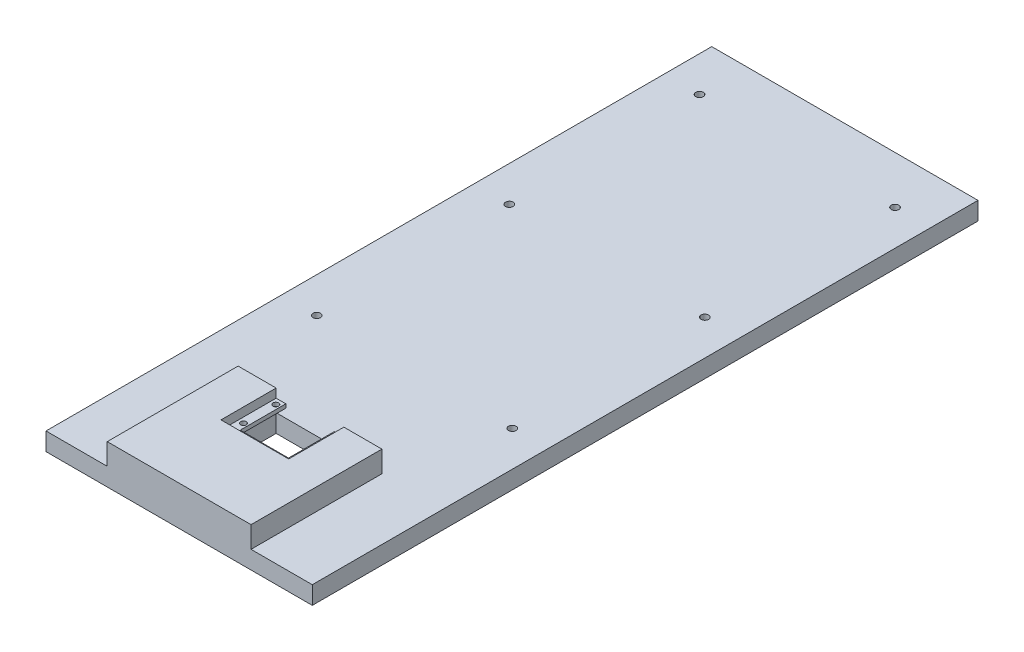
SolidWorks part; units mm, degrees
note: The reader was unsure of these and kept them because the rebuilt part matched: shared geometry of "Sketch5<5>".
ref_plane "Front Plane" through (0, 0, 0) normal (0, 0, 1) x (1, 0, 0)
ref_plane "Top Plane" through (0, 0, 0) normal (0, 1, 0) x (1, 0, 0)
ref_plane "Right Plane" through (0, 0, 0) normal (1, 0, 0) x (0, 0, -1)
sketch "Sketch2" plane through (0, 0, 0) normal (0, 1, 0) x (1, 0, 0)
  line L0 (-15, 0) -> (15, 0) construction
  line L1 (-15, 17) -> (15, 17) construction
  line L2 (-15, 17) -> (-15, -17) construction
  line L3 (-15, -17) -> (15, -17) construction
  line L4 (15, 17) -> (15, -17) construction
  line L5 (-8.5, -23.3) -> (8.5, -23.3) construction
  line L6 (0, 1064.2) -> (0, 64.2) construction
  line L8 (-17.8, -26.1) -> (17.8, -26.1) construction
  line L9 (-17.8, -26.1) -> (-17.8, 24.5) construction
  line L11 (17.8, -26.1) -> (17.8, 24.5) construction
  line L12 (-12.2, 24.5) -> (12.2, 24.5) construction
  line L13 (-12.2, 24.5) -> (-12.2, -20.5) construction
  line L14 (-12.2, -20.5) -> (12.2, -20.5) construction
  line L15 (12.2, 24.5) -> (12.2, -20.5) construction
  line L20 (-12.2, 24.5) -> (-17.8, 24.5) construction
  line L21 (12.2, 24.5) -> (17.8, 24.5) construction
  line L22 (-12.7, 25) -> (-12.7, -21)
  line L23 (-12.7, -21) -> (12.7, -21)
  line L24 (12.7, 25) -> (12.7, -21)
  line L25 (-12.7, 25) -> (12.7, 25)
  line L26 (37.8, -46.1) -> (37.8, 44.5)
  line L30 (-37.8, -46.1) -> (-37.8, 44.5)
  line L32 (37.8, -0.8) -> (37.8, -65.8)
  line L33 (37.8, -65.8) -> (37.8, 64.2)
  line L34 (37.8, 64.2) -> (-37.8, 64.2)
  line L35 (-37.8, 64.2) -> (-37.8, -65.8)
  line L36 (-37.8, -65.8) -> (37.8, -65.8)
  line L39 (-22.8, -62.2) -> (-37.8, -62.2) construction
  line L41 (9.15, 64.2) -> (9.15, 63.8) construction
  line L42 (9.15, -65.8) -> (-9.05, -65.8) construction
  line L44 (37.8, -65.8) -> (37.8, -62.2) construction
  line L45 (37.8, -62.2) -> (22.8, -62.2) construction
  line L48 (9.15, 64.2) -> (9.15, 63.8)
  line L54 (37.8, -65.8) -> (37.8, 64.2)
  line L55 (37.8, -65.8) -> (37.8, -0.8)
  line L56 (37.8, -0.8) -> (-37.8, -0.8) construction
  line L57 (9.15, 64.2) -> (9.15, 63.8)
  line L59 (9.15, -35.8) -> (9.15, 34.2) construction
  line L60 (7.55, 64.2) -> (-9.05, 64.2) construction
  line L61 (9.15, 63.8) -> (9.15, 64.2) construction
  line L62 (9.15, 34.2) -> (9.15, -35.8) construction
  line L67 (7.55, -40.6) -> (7.55, 34.2) construction
  line L68 (0, -65.8) -> (0, -1091.9268) construction
  line L70 (12.2, 44.5) -> (37.8, 44.5) construction
  line L71 (-12.2, 44.5) -> (-37.8, 44.5) construction
  line L72 (-12.2, 44.5) -> (12.2, 44.5) construction
  line L73 (-37.8, -46.1) -> (37.8, -46.1) construction
  line L74 (-9.05, -35.8) -> (-9.05, 34.2) construction
  line L76 (7.55, 34.2) -> (37.8, 34.2)
  line L77 (37.8, 34.2) -> (-37.8, 34.2)
  line L78 (7.55, -35.8) -> (37.8, -35.8)
  line L79 (37.8, -35.8) -> (-37.8, -35.8)
  line L80 (37.8, 64.2) -> (37.8, -65.8)
  line L81 (37.8, 64.2) -> (32.8, 64.2)
  line L82 (-37.8, 64.2) -> (-32.8, 64.2)
  line L83 (32.8, 64.2) -> (22.8, 64.2)
  line L84 (32.8, 64.2) -> (32.8, -65.8)
  line L85 (32.8, -65.8) -> (22.8, -65.8)
  line L86 (22.8, 64.2) -> (22.8, -65.8)
  line L88 (-32.8, 64.2) -> (-22.8, 64.2)
  line L89 (-32.8, 64.2) -> (-32.8, -65.8)
  line L90 (-32.8, -65.8) -> (-22.8, -65.8)
  line L91 (-22.8, 64.2) -> (-22.8, -65.8)
  line L94 (0, 34.2) -> (0, -35.8) construction
  circle A0 centre (0, 12.5) radius 11 construction
  circle A1 centre (-15, 17) radius 1.5
  circle A2 centre (-15, 0) radius 1.5
  circle A3 centre (-15, -17) radius 1.5
  circle A4 centre (15, 17) radius 1.5
  circle A5 centre (15, 0) radius 1.5
  circle A6 centre (15, -17) radius 1.5
  circle A7 centre (-8.5, -23.3) radius 1.5
  circle A8 centre (8.5, -23.3) radius 1.5
  point P6 (0, 0)
  point P11 (0, -23.3)
  point P19 (0, -26.1)
  point P24 (0, -20.5)
  point P58 (-7.45, -62.2)
  point P59 (0, -62.2)
  point P61 (9.15, -62.2)
  point P66 (-9.05, 42.2)
  point P68 (-9.05, -62.2)
  point P71 (-9.05, 62.2)
  dimension "D3" = 22
  dimension "D12" = 3
  dimension "D1" = 17
  dimension "D2" = 30
  dimension "D4" = 4.5
  dimension "D5" = 35.8
  dimension "D6" = 17
  dimension "D7" = 50.6
  dimension "D8" = 35.6
  dimension "D9" = 12
  dimension "D10" = 24.4
  dimension "D11" = 33
  dimension "D13" = 0.5
  dimension "D21" = 130
  dimension "D14" = 20
extrude "Boss-Extrude1" add sketch "Sketch2" along normal blind 2
sketch "Sketch5" plane through (0, 0, 0) normal (0, -1, 0) x (1, 0, 0)
  line L0 (16.5, 0) -> (13.5, 0) construction
  line L1 (37.8, 65.8) -> (-37.8, 65.8)
  line L2 (37.8, 65.8) -> (37.8, 30.8)
  line L4 (-37.8, 65.8) -> (-37.8, -64.2)
  line L5 (-37.8, -64.2) -> (37.8, -64.2)
  line L6 (-37.8, 65.8) -> (-37.8, -64.2)
  line L7 (37.8, 65.8) -> (-37.8, 65.8)
  line L11 (37.8, 65.8) -> (-37.8, 65.8)
  line L12 (-12.7, 21) -> (-12.7, -25)
  line L13 (-12.7, 21) -> (-12.7, -25)
  line L14 (12.7, 21) -> (-12.7, 21)
  line L15 (12.7, 21) -> (-12.7, 21)
  line L20 (-37.8, 65.8) -> (-37.8, 30.8)
  line L21 (37.8, -64.2) -> (-37.8, -64.2)
  line L22 (37.8, -64.2) -> (37.8, -29.2)
  line L24 (-37.8, -64.2) -> (-37.8, -29.2)
  line L26 (37.8, 30.8) -> (37.8, -29.2)
  line L30 (-37.8, -29.2) -> (-37.8, 30.8)
  line L33 (37.8, 65.8) -> (-37.8, 65.8)
  line L34 (37.8, 65.8) -> (37.8, -64.2)
  line L35 (37.8, -64.2) -> (-37.8, -64.2)
  line L36 (-37.8, 65.8) -> (-37.8, -64.2)
  line L37 (-16.5, 0) -> (-13.5, 0) construction
  line L38 (-13.5, 0) -> (-16.5, 0) construction
  line L39 (13.5, 0) -> (15, 0) construction
  line L40 (0, 0) -> (0, -3)
  line L41 (0, -3) -> (37.8, -3)
  line L42 (37.8, -3) -> (-37.8, -3)
  line L43 (-37.8, -3) -> (-17.8, -3)
  line L44 (-37.8, -64.2) -> (37.8, -64.2)
  line L45 (37.8, -64.2) -> (37.8, 65.8)
  line L46 (37.8, -64.2) -> (37.8, 65.8)
  line L47 (12.7, -25) -> (12.7, 21)
  line L48 (12.7, -25) -> (12.7, 21)
  line L49 (-12.7, -25) -> (12.7, -25)
  line L50 (-12.7, -25) -> (12.7, -25)
  line L51 (-17.8, -3) -> (-17.8, 27)
  line L52 (17.8, -3) -> (17.8, 27)
  line L53 (17.8, 27) -> (-17.8, 27)
  line L55 (-37.8, -64.2) -> (37.8, -64.2)
  line L56 (-37.8, -64.2) -> (-37.8, -3)
  line L57 (-37.8, -3) -> (37.8, -3)
  line L58 (37.8, -64.2) -> (37.8, -3)
  circle A11 centre (-15, -17) radius 1.5
  circle A18 centre (-15, 0) radius 1.5 construction
  circle A19 centre (-8.5, 23.3) radius 1.5 construction
  circle A20 centre (8.5, 23.3) radius 1.5 construction
  circle A21 centre (-15, 17) radius 1.5 construction
  circle A28 centre (-15, 0) radius 1.5
  circle A29 centre (-8.5, 23.3) radius 1.5
  circle A30 centre (8.5, 23.3) radius 1.5
  circle A31 centre (-15, 17) radius 1.5
  circle A42 centre (15, 17) radius 2.23
  circle A43 centre (15, 0) radius 2.23
  circle A44 centre (15, -17) radius 2.25
  circle A45 centre (-15, -17) radius 2.25
  circle A46 centre (-15, 0) radius 2.23
  circle A47 centre (-15, 17) radius 2.23
  circle A48 centre (-8.5, 23.3) radius 2.23
  circle A49 centre (8.5, 23.3) radius 2.23
  circle A50 centre (-15, -17) radius 1.5
  circle A51 centre (15, -17) radius 1.5
  circle A52 centre (15, -17) radius 1.5
  circle A53 centre (15, 0) radius 1.5
  circle A54 centre (15, 0) radius 1.5
  circle A55 centre (15, 17) radius 1.5
  circle A56 centre (15, 17) radius 1.5
  line M12 (-37.8, 65.8) -> (-37.8, -64.2)
  line M13 (-37.8, -64.2) -> (37.8, -64.2)
  line M14 (37.8, -64.2) -> (37.8, 65.8)
  line M15 (37.8, 65.8) -> (-37.8, 65.8)
  line M25 (-12.7, -25) -> (-12.7, 21)
  line M27 (12.7, 21) -> (12.7, -25)
  line M28 (12.7, -25) -> (-12.7, -25)
  dimension "D9" = 4.46
  dimension "D2" = 4.46
  dimension "D3" = 4.46
  dimension "D10" = 4.46
  dimension "D11" = 4.46
  dimension "D12" = 4.46
  dimension "D1" = 0
  dimension "D4" = 0
  dimension "D5" = 0
  dimension "D6" = 0
  dimension "D7" = 0
  dimension "D8" = 0
extrude "Boss-Extrude3" add sketch "Sketch5" along normal blind 4.62 contours L53 L52 L42 L34 L6 L51 M14 M15 M12
extrude "Cut-Extrude3" cut sketch "Sketch5<5>" against normal blind 10 contours L42 L36 L41 A45 A44 M25 M12 M13 M14 M27 M28
sketch "Sketch5<5>" plane through (0, 0, 0) normal (0, -1, 0) x (1, 0, 0) same geometry as "Sketch5"
sketch "Sketch6" plane through (0, 2, 0) normal (0, 1, 0) x (1, 0, 0)
  line L0 (-17.8, 3) -> (-17.8, -25.9964)
  line L1 (-17.8, -25.9964) -> (-17.8, 3)
  line L2 (-12.7, 3) -> (-17.8, 3)
  line L3 (12.7, 3) -> (17.8, 3)
  line L4 (17.8, 3) -> (17.8, -25.9964)
  line L5 (17.8, -25.9964) -> (-17.8, -25.9964)
  line L6 (0, -65.8) -> (70, -65.8)
  line L7 (70, -65.8) -> (-70, -65.8)
  line L8 (37.8, -65.8) -> (37.8, 3)
  line L9 (37.8, 3) -> (12.7, 3)
  line L10 (12.7, 3) -> (12.7, -21)
  line L11 (12.7, -21) -> (-12.7, -21)
  line L12 (-12.7, -21) -> (-12.7, 3)
  line L13 (-12.7, 3) -> (-37.8, 3)
  line L14 (-37.8, 3) -> (-37.8, -65.8)
  line L15 (-37.8, -65.8) -> (37.8, -65.8)
  line L17 (17.8, 3) -> (12.7, 3)
  line L18 (12.7, 3) -> (12.7, -21)
  line L19 (12.7, -21) -> (-12.7, -21)
  line L20 (-12.7, -21) -> (-12.7, 3)
  line L21 (-12.7, 3) -> (-17.8, 3)
  line L23 (-37.8, -65.8) -> (37.8, -65.8)
  line L24 (-70, -65.8) -> (-70, 284.2)
  line L25 (-70, 284.2) -> (70, 284.2)
  line L26 (70, 284.2) -> (70, -65.8)
  line L27 (17.8, 3) -> (-17.8, 3)
  line L28 (-17.8, 3) -> (17.8, 3)
  line L29 (17.8, -25.9964) -> (-17.8, -25.9964)
  line L30 (-17.8, 3) -> (-17.8, -25.9964)
  line L32 (-17.8, 3) -> (17.8, 3)
  line L33 (-17.8, 3) -> (-17.8, -25.9964)
  line L34 (-17.8, -25.9964) -> (17.8, -25.9964)
  line L35 (17.8, 3) -> (17.8, -25.9964)
  line L36 (70, 284.2) -> (-70, 284.2)
  line L37 (70, 284.2) -> (70, -65.8)
  line L38 (70, -65.8) -> (-70, -65.8)
  line L39 (-70, 284.2) -> (-70, -65.8)
  circle A0 centre (-15, 0) radius 1.5 construction
  circle A1 centre (-15, -17) radius 1.5 construction
  circle A2 centre (-8.5, -23.3) radius 1.5 construction
  circle A3 centre (8.5, -23.3) radius 1.5 construction
  circle A4 centre (15, -17) radius 1.5 construction
  circle A5 centre (15, 0) radius 1.5 construction
  circle A6 centre (-15, 0) radius 1.5
  circle A7 centre (-15, -17) radius 1.5
  circle A8 centre (-8.5, -23.3) radius 1.5
  circle A9 centre (8.5, -23.3) radius 1.5
  circle A10 centre (15, -17) radius 1.5
  circle A11 centre (15, 0) radius 1.5
  line M15 (37.8, -65.8) -> (37.8, 3)
  line M16 (37.8, 3) -> (12.7, 3)
  line M20 (-12.7, 3) -> (-37.8, 3)
  line M21 (-37.8, 3) -> (-37.8, -65.8)
  line M22 (-37.8, -65.8) -> (37.8, -65.8)
  dimension "D1" = 0
extrude "Boss-Extrude4" add sketch "Sketch6" along normal blind 4.62 contours L4 L5 L0 M20 M21 M22 M15 M16
sketch "Sketch8" plane through (0, -4.62, 0) normal (0, -1, 0) x (1, 0, 0)
  line L0 (0, 27) -> (0, -22.6432) construction
  line L1 (37.8, 65.8) -> (-37.8, 65.8) construction
  line L2 (0, 65.8) -> (-70, 65.8)
  line L4 (-70, 65.8) -> (70, 65.8)
  line L5 (-70, 65.8) -> (-70, -284.2)
  line L6 (-70, -284.2) -> (70, -284.2)
  line L7 (70, 65.8) -> (70, -284.2)
  line L10 (-37.8, 65.8) -> (37.8, 65.8)
  line L12 (-17.8, -3) -> (17.8, -3)
  line L14 (-17.8, -3) -> (17.8, -3)
  line L15 (-17.8, -3) -> (-17.8, 27)
  line L16 (-17.8, 27) -> (17.8, 27)
  line L17 (17.8, -3) -> (17.8, 27)
extrude "Boss-Extrude10" add sketch "Sketch8" along normal blind 4.63
sketch "Sketch9" plane through (0, -9.25, 0) normal (0, -1, 0) x (1, 0, 0)
  line L0 (-17.8, -3) -> (-17.8, 27) construction
  line L1 (-17.8, -3) -> (17.8, -3) construction
  line L2 (17.8, 27) -> (17.8, -3) construction
  line L3 (-17.8, 27) -> (17.8, 27) construction
  line L4 (70, -284.2) -> (70, 65.8)
  line L5 (70, 65.8) -> (-70, 65.8)
  line L6 (-70, 65.8) -> (-70, -284.2)
  line L7 (-70, -284.2) -> (70, -284.2)
  line L8 (70, -284.2) -> (70, 65.8)
  line L9 (70, 65.8) -> (-70, 65.8)
  line L10 (-70, 65.8) -> (-70, -284.2)
  line L11 (-70, -284.2) -> (70, -284.2)
  line L12 (-17.8, -3) -> (-17.8, 27)
  line L13 (-17.8, -3) -> (17.8, -3)
  line L14 (17.8, 27) -> (17.8, -3)
  line L15 (-17.8, 27) -> (17.8, 27)
  dimension "D1" = 0
extrude "Boss-Extrude11" add sketch "Sketch9" along normal blind 4.8
sketch "Sketch10" plane through (0, -4.62, 0) normal (0, 1, 0) x (1, 0, 0)
  line L0 (0, 284.2) -> (0, -65.8) construction
  line L1 (70, 284.2) -> (-70, 284.2)
  line L2 (70, 284.2) -> (70, -65.8)
  line L3 (70, -65.8) -> (-70, -65.8)
  line L4 (-70, 284.2) -> (-70, -65.8)
  line L5 (0, -65.8) -> (0, 284.2) construction
  line L6 (0, 284.2) -> (51.4, 284.2)
  line L7 (51.4, 281.7) -> (51.4, -65.8) construction
  line L8 (51.4, 284.2) -> (51.4, 259.2)
  line L9 (51.4, 259.2) -> (51.4, 234.2)
  line L10 (51.4, 234.2) -> (51.4, 209.2)
  line L11 (51.4, 209.2) -> (51.4, 184.2)
  line L12 (51.4, 184.2) -> (51.4, 159.2)
  line L13 (51.4, 159.2) -> (51.4, 132.95)
  line L14 (51.4, 132.95) -> (51.4, 107.95)
  line L15 (51.4, 107.95) -> (51.4, 82.95)
  line L16 (51.4, 82.95) -> (51.4, 57.95)
  line L17 (51.4, 57.95) -> (51.4, 32.95)
  line L18 (51.4, 32.95) -> (51.4, 7.95)
  line L19 (51.4, 7.95) -> (51.4, -17.05)
  line L20 (-51.4, 284.2) -> (-51.4, 259.2)
  circle A0 centre (51.4, 259.2) radius 2
  circle A1 centre (51.4, 57.95) radius 2
  circle A2 centre (51.4, 159.2) radius 2
  circle A3 centre (-51.4, 57.95) radius 2
  circle A4 centre (-51.4, 259.2) radius 2
  circle A5 centre (-51.4, 159.2) radius 2
extrude "Cut-Extrude4" cut sketch "Sketch10" against normal through all
